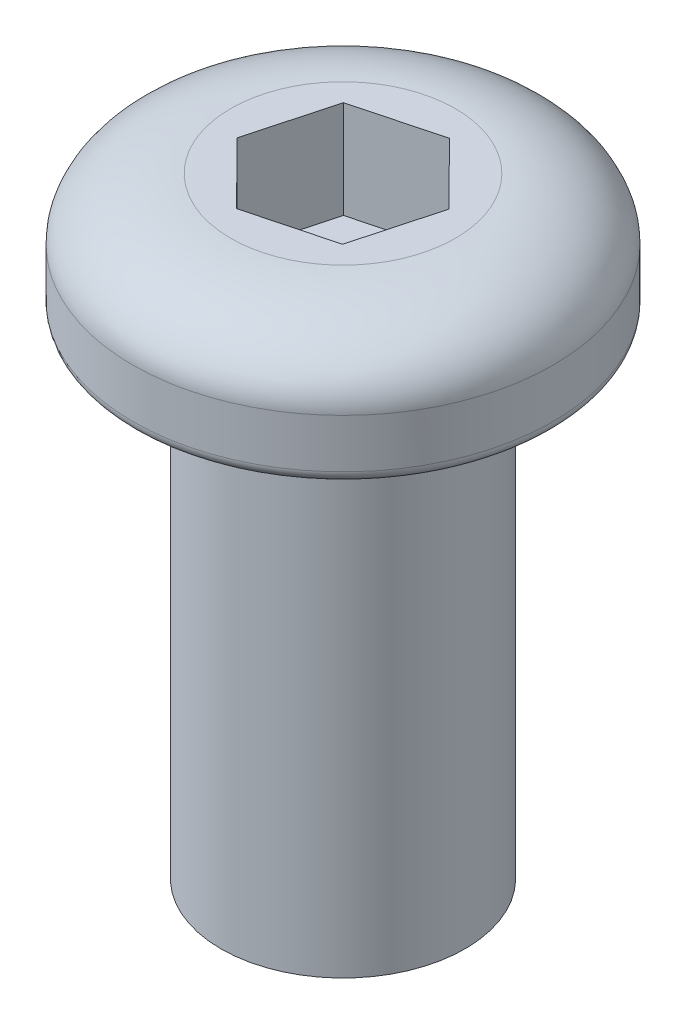
SolidWorks part; units mm, degrees
material "Chrome Stainless Steel"
ref_plane "Front Plane" through (0, 0, 0) normal (0, 0, 1) x (1, 0, 0)
ref_plane "Top Plane" through (0, 0, 0) normal (0, 1, 0) x (1, 0, 0)
ref_plane "Right Plane" through (0, 0, 0) normal (1, 0, 0) x (0, 0, -1)
sketch "Sketch1" plane through (0, 0, 0) normal (0, 1, 0) x (1, 0, 0)
  circle A0 centre (0, 0) radius 5
  dimension "D1" = 10
extrude "Boss-Extrude1" add sketch "Sketch1" along normal blind 20
sketch "Sketch2" plane through (0, 20, 0) normal (0, 1, 0) x (1, 0, 0)
  circle A0 centre (0, 0) radius 8.6
  dimension "D1" = 17.2
extrude "Boss-Extrude2" add sketch "Sketch2" along normal blind 5
fillet "Fillet1" radius 2.5 1 edges at (0, 25, 8.6) second distance 4 first distance on face at (0, 25, 8.6)
sketch "Sketch3" plane through (0, 25, 0) normal (0, 1, 0) x (1, 0, 0)
  line L1 (2.501, -2.5204) -> (3.4332, 0.9057)
  line L2 (3.4332, 0.9057) -> (0.9322, 3.4261)
  line L3 (0.9322, 3.4261) -> (-2.501, 2.5204)
  line L4 (-2.501, 2.5204) -> (-3.4332, -0.9057)
  line L5 (-3.4332, -0.9057) -> (-0.9322, -3.4261)
  line L6 (-0.9322, -3.4261) -> (2.501, -2.5204)
  circle A0 centre (0, 0) radius 3.075 construction
  dimension "D1" = 6.15
extrude "Cut-Extrude1" cut sketch "Sketch3" against normal blind 4
fillet "Fillet2" radius 0.5 1 edges at (0, 20, 8.6)
